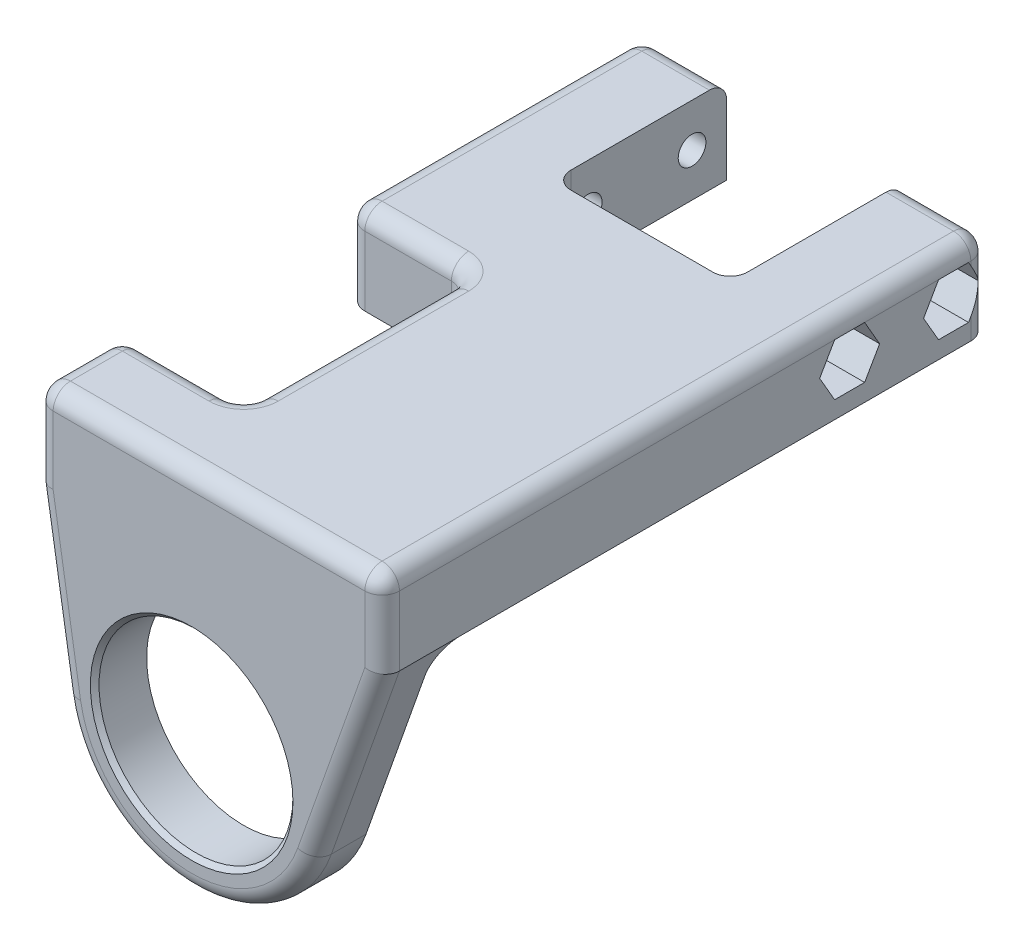
SolidWorks part; units mm, degrees
ref_plane "Top Plane" through (0, 0, 0) normal (0, 0, 1) x (1, 0, 0)
ref_plane "Right Plane" through (0, 0, 0) normal (0, 1, 0) x (1, 0, 0)
ref_plane "Front Plane" through (0, 0, 0) normal (1, 0, 0) x (0, 0, -1)
sketch "Sketch1" plane through (0, 0, 0) normal (0, 0, 1) x (1, 0, 0)
  line L0 (0, 0) -> (0, 27.25) construction
  line L1 (22, 27.25) -> (22, 17.25)
  line L2 (-18, 27.25) -> (22, 27.25)
  line L3 (-18, 27.25) -> (-18, 17.25)
  line L4 (22, 17.25) -> (14.1439, -4.9951)
  line L5 (-18, 17.25) -> (-14.8058, -2.406)
  arc A0 (-14.8058, -2.406) -> (14.1439, -4.9951) centre (0, 0) ccw construction
  circle A1 centre (0, 0) radius 11 construction
  circle A2 centre (0, 0) radius 4 construction
  arc A3 (-14.8058, -2.406) -> (14.1439, -4.9951) centre (0, 0) ccw
  dimension "D1" = 30
  dimension "D2" = 22
  dimension "D3" = 8
  dimension "D6" = 10
  dimension "D4" = 27.25
  dimension "D5" = 40
  dimension "D7" = 18
extrude "Boss-Extrude1" add sketch "Sketch1" along normal blind 6
sketch "Sketch2" plane through (0, 0, 6) normal (0, 0, 1) x (1, 0, 0)
  circle A2 centre (0, 0) radius 11.2
  circle A3 centre (0, 0) radius 11.2
  dimension "D1" = 0.2
extrude "Cut-Extrude1" cut sketch "Sketch2" against normal through all
sketch "Sketch3" plane through (0, 0, 0) normal (0, 0, -1) x (-1, 0, 0)
  line L0 (18, 27.25) -> (-22, 27.25) construction
  line L1 (-22, 27.25) -> (-12, 27.25) construction
  line L2 (-22, 27.25) -> (-22, 17.25) construction
  line L3 (-22, 17.25) -> (-12, 17.25) construction
  line L4 (-12, 27.25) -> (-12, 17.25) construction
  line L5 (8, 27.25) -> (18, 27.25) construction
  line L6 (8, 27.25) -> (8, 17.25) construction
  line L7 (8, 17.25) -> (18, 17.25) construction
  line L8 (18, 27.25) -> (18, 17.25) construction
  line L9 (-12, 22.25) -> (8, 22.25) construction
  line L11 (-2, 22.25) -> (-2, 27.25) construction
  line L13 (-22, 27.25) -> (18, 27.25)
  line L14 (-22, 27.25) -> (-22, 17.25)
  line L15 (-22, 17.25) -> (18, 17.25)
  line L16 (18, 27.25) -> (18, 17.25)
  point P12 (-2, 22.25)
  dimension "D1" = 20
extrude "Boss-Extrude2" add sketch "Sketch3" along normal blind 44
sketch "Sketch4" plane through (0, 0, -44) normal (0, 0, -1) x (-1, 0, 0)
  line L0 (-22, 17.25) -> (18, 17.25) construction
  line L1 (-22, 27.25) -> (-12.2, 27.25)
  line L2 (-22, 27.25) -> (-22, 17.25)
  line L3 (-22, 17.25) -> (-12.2, 17.25)
  line L4 (-12.2, 27.25) -> (-12.2, 17.25)
  line L5 (8.2, 27.25) -> (18, 27.25)
  line L6 (8.2, 27.25) -> (8.2, 17.25)
  line L7 (8.2, 17.25) -> (18, 17.25)
  line L8 (18, 27.25) -> (18, 17.25)
  line L9 (-12, 27.25) -> (-12, 17.25) construction
  line L10 (8, 27.25) -> (8, 17.25) construction
  point P10 (0, 0)
  point P11 (0, 0)
  point P14 (-12.78, 18.03)
  point P15 (0, 0)
  point P16 (-13.3556, 18.2153)
  point P21 (0, 0)
  point P22 (0, 0)
  point P23 (9.2322, 17.25)
  dimension "D1" = 0.2
  dimension "D2" = 0.2
extrude "Boss-Extrude3" add sketch "Sketch4" along normal blind 20
fillet "Fillet1" radius 3 1 edges at (2, 17.25, 0)
sketch "Sketch5" plane through (12.2, 0, 0) normal (-1, 0, 0) x (0, 0, 1)
  line L0 (-64, 22.25) -> (-44, 22.25) construction
  line L1 (-64, 17.25) -> (-64, 27.25) construction
  line L2 (-44, 17.25) -> (-44, 27.25) construction
  line L3 (-54, 27.25) -> (-54, 22.25) construction
  line L4 (-64, 27.25) -> (-44, 27.25) construction
  circle A0 centre (-60, 22.25) radius 1.75
  circle A1 centre (-48, 22.25) radius 1.75
  dimension "D1" = 3.5
  dimension "D2" = 12
hole_wizard "CBORE for M3 Hex Socket Head Cap Screw1" positions "Sketch6" profile "Sketch7" counterbore size "M3" standard "ISO" end condition through all
sketch "Sketch6" plane through (-18, 0, 0) normal (-1, 0, 0) x (0, 0, 1)
  point P0 (-60, 22.25)
  point P3 (-48, 22.25)
sketch "Sketch7" plane through (-18, 22.25, -60) normal (0, 1, 0) x (0, 0, 1)
  line L0 (0, 0) -> (0, 40)
  line L1 (0, 40) -> (1.6, 40)
  line L3 (1.6, 40) -> (1.6, 3.4)
  line L4 (1.6, 3.4) -> (3.25, 3.4)
  line L5 (3.25, 3.4) -> (3.25, 0)
  line L7 (3.25, 0) -> (0, 0)
  line L11 (0, -6.35) -> (0, 107.95) construction
  dimension "Thru Hole Dia." = 3.2
  dimension "Thru Hole Depth" = 40
  dimension "C'Bore Dia." = 6.5
  dimension "C'Bore Depth" = 3.4
sketch "Sketch8" plane through (22, 0, 0) normal (1, 0, 0) x (0, 0, -1)
  line L1 (49.7321, 25.25) -> (46.2679, 25.25)
  line L2 (46.2679, 25.25) -> (44.5359, 22.25)
  line L3 (44.5359, 22.25) -> (46.2679, 19.25)
  line L4 (46.2679, 19.25) -> (49.7321, 19.25)
  line L5 (49.7321, 19.25) -> (51.4641, 22.25)
  line L6 (51.4641, 22.25) -> (49.7321, 25.25)
  line L7 (58.2679, 25.25) -> (56.5359, 22.25)
  line L8 (56.5359, 22.25) -> (58.2679, 19.25)
  line L9 (58.2679, 19.25) -> (61.7321, 19.25)
  line L10 (61.7321, 19.25) -> (63.4641, 22.25)
  line L11 (63.4641, 22.25) -> (61.7321, 25.25)
  line L12 (61.7321, 25.25) -> (58.2679, 25.25)
  circle A0 centre (48, 22.25) radius 3 construction
  circle A1 centre (60, 22.25) radius 3 construction
  dimension "D1" = 6
extrude "Cut-Extrude3" cut sketch "Sketch8" against normal offset from surface (5.8 mm away) 4 up to face at (12.2, 23.85, -60)
sketch "Sketch9" plane through (0, 27.25, 0) normal (0, 1, 0) x (1, 0, 0)
  line L0 (-18, -6) -> (-18, 64) construction
  line L1 (-18, 30) -> (-4, 30)
  line L2 (-18, 30) -> (-18, 4)
  line L3 (-18, 4) -> (-4, 4)
  line L4 (-4, 30) -> (-4, 4)
  line L5 (22, -6) -> (-18, -6) construction
  dimension "D1" = 36
  dimension "D2" = 10
  dimension "D3" = 14
extrude "Cut-Extrude4" cut sketch "Sketch9" against normal through all
fillet "Fillet2" radius 2 2 edges at (-4, 22.25, -4) (-4, 22.25, -30)
fillet "Fillet3" radius 2 2 edges at (12.2, 22.25, -44) (-8.2, 22.25, -44)
fillet "Fillet4" radius 2 9 edges at (-16.4029, 7.422, 6) (-1.3362, -14.9404, 6) (18.0719, 6.1275, 6) (-18, 22.25, 6) (22, 22.25, 6) (-18, 22.25, -4) (-18, 22.25, -30) (22, 22.25, -64) (-18, 22.25, -64)
fillet "Fillet5" radius 2 17 edges at (-12.1, 27.25, -64) (-17.4142, 27.25, -63.4142) (-18, 27.25, -47) (-17.4142, 27.25, -30.5858) (-11, 27.25, -30) (-4.5858, 27.25, -29.4142) (-4, 27.25, -17) (-4.5858, 27.25, -4.5858) (-11, 27.25, -4) (-17.4142, 27.25, -3.4142) (-18, 27.25, 1) (-17.4142, 27.25, 5.4142) (2, 27.25, 6) (21.4142, 27.25, 5.4142) (16.1, 27.25, -64) (21.4142, 27.25, -63.4142) (22, 27.25, -29)
chamfer "Chamfer1" distance 0.5 angle 45 1 edges at (11.2, 0, 6)
